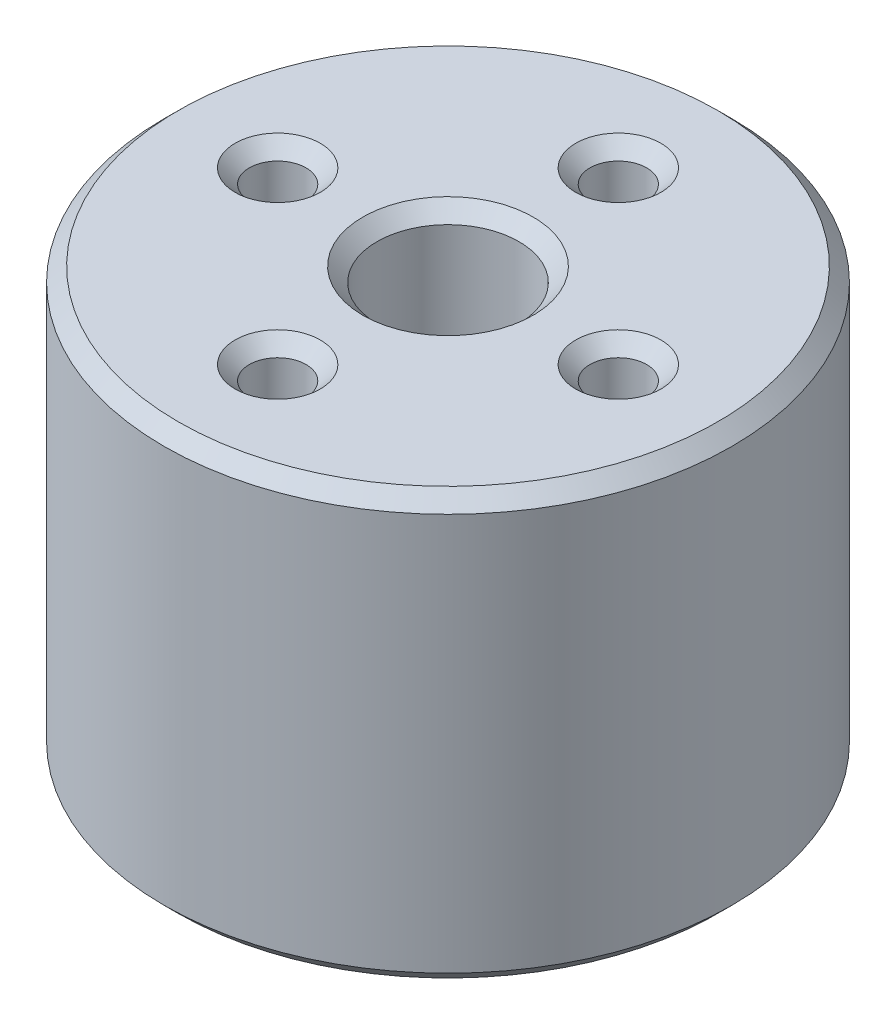
SolidWorks part; units mm, degrees
ref_plane "前视基准面" through (0, 0, 0) normal (0, 0, 1) x (1, 0, 0)
ref_plane "上视基准面" through (0, 0, 0) normal (0, 1, 0) x (1, 0, 0)
ref_plane "右视基准面" through (0, 0, 0) normal (1, 0, 0) x (0, 0, -1)
other "Configuration Table"
sketch "草图1" plane through (0, 0, 0) normal (0, 1, 0) x (1, 0, 0)
  circle A0 centre (0, 0) radius 10
  circle A1 centre (0, 0) radius 2.5
  dimension "D1" = 20
  dimension "D2" = 5
extrude "凸台-拉伸1" add sketch "草图1" along normal blind 15
sketch "草图2" plane through (0, 15, 0) normal (0, 1, 0) x (1, 0, 0)
  circle A0 centre (-6, 0) radius 1
  dimension "D1" = 2
  dimension "D2" = 6
extrude "切除-拉伸1" cut sketch "草图2" against normal blind 15
pattern_circular "阵列(圆周)1" count 4 over 360 about axis through (0, 15, 0) along (0, -1, 0) of "切除-拉伸1"
chamfer "倒角1" distance 0.5 angle 45 12 edges at (0, 0, 10) (0, 15, 10) (-1, 15, -6) (-1, 0, -6) (6, 15, -1) (6, 0, -1) (0, 0, 2.5) (0, 15, 2.5) (1, 15, 6) (1, 0, 6) (-6, 15, 1) (-6, 0, 1)
